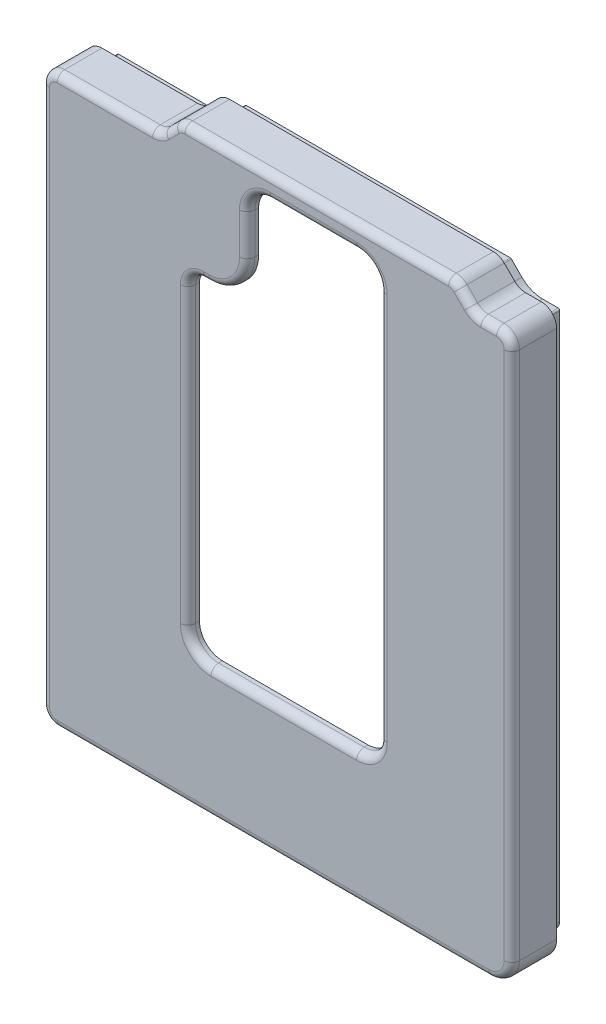
SolidWorks part; units mm, degrees
ref_plane "Front Plane" through (0, 0, 0) normal (0, 0, 1) x (1, 0, 0)
ref_plane "Top Plane" through (0, 0, 0) normal (0, 1, 0) x (1, 0, 0)
ref_plane "Right Plane" through (0, 0, 0) normal (1, 0, 0) x (0, 0, -1)
sketch "ard ref" plane through (0, 0, 0) normal (0, 0, 1) x (1, 0, 0)
  line L0 (2.0155, -3.0374) -> (2.0155, -101.7244) construction
  line L1 (27.0155, -3.0374) -> (27.0155, -101.7244) construction
  line L2 (-17.0643, -59.6174) -> (41.2757, -59.6174) construction
  line L3 (2.0155, -16.358) -> (9.7357, -16.358) construction
  line L4 (27.1007, -75.1174) -> (8.9057, -75.1174)
  line L5 (8.9057, -75.1174) -> (8.9057, -76.6174)
  line L6 (8.9057, -76.6174) -> (27.1007, -76.6174)
  line L7 (27.1007, -76.6174) -> (27.1007, -75.1174)
  line L9 (8.9057, -75.1174) -> (8.9057, -76.6174)
  line L10 (8.9057, -76.6174) -> (27.1007, -76.6174)
  line L11 (27.1007, -76.6174) -> (27.1007, -75.1174)
  line L12 (9.7357, -16.358) -> (9.7357, -0.0374) construction
  line L20 (44.2757, -73.6174) -> (44.2757, -4.5774)
  line L21 (42.2757, -2.5774) -> (40.221, -2.5774)
  line L22 (38.8068, -1.9916) -> (37.4383, -0.6232)
  line L23 (36.0241, -0.0374) -> (1.6013, -0.0374)
  line L24 (0.1871, -0.6232) -> (-1.1814, -1.9916)
  line L25 (-2.5956, -2.5774) -> (-15.0643, -2.5774)
  line L26 (-17.0643, -4.5774) -> (-17.0643, -74.6174)
  line L27 (-15.0643, -76.6174) -> (-4.3943, -76.6174)
  line L28 (-4.3943, -76.6174) -> (-4.3943, -75.1174)
  line L29 (42.7757, -4.0774) -> (42.7757, -75.1174)
  line L30 (42.7757, -4.0774) -> (42.7757, -75.1174)
  line L31 (42.7757, -75.1174) -> (38.1007, -75.1174)
  line L32 (42.7757, -75.1174) -> (38.1007, -75.1174)
  line L33 (-4.3943, -75.1174) -> (-15.5643, -75.1174)
  line L34 (-4.3943, -75.1174) -> (-15.5643, -75.1174)
  line L35 (-15.5643, -75.1174) -> (-15.5643, -4.0774)
  line L36 (-15.5643, -75.1174) -> (-15.5643, -4.0774)
  line L37 (-15.5643, -4.0774) -> (-1.1458, -4.0774)
  line L38 (38.1007, -75.1174) -> (38.1007, -76.6174)
  line L39 (38.1007, -76.6174) -> (41.2757, -76.6174)
  line L40 (44.2757, -73.6174) -> (44.2757, -4.5774)
  line L41 (42.2757, -2.5774) -> (40.221, -2.5774)
  line L42 (38.8068, -1.9916) -> (37.4383, -0.6232)
  line L43 (36.0241, -0.0374) -> (1.6013, -0.0374)
  line L44 (0.1871, -0.6232) -> (-1.1814, -1.9916)
  line L45 (-2.5956, -2.5774) -> (-15.0643, -2.5774)
  line L46 (-17.0643, -4.5774) -> (-17.0643, -74.6174)
  line L47 (-15.0643, -76.6174) -> (-4.3943, -76.6174)
  line L48 (-4.3943, -76.6174) -> (-4.3943, -75.1174)
  line L58 (38.1007, -75.1174) -> (38.1007, -76.6174)
  line L59 (38.1007, -76.6174) -> (41.2757, -76.6174)
  line L77 (27.1007, -75.1174) -> (8.9057, -75.1174)
  line L93 (-15.5643, -4.0774) -> (-1.1458, -4.0774)
  line L94 (-1.1458, -4.0774) -> (1.3942, -1.5374)
  line L95 (-1.1458, -4.0774) -> (1.3942, -1.5374)
  line L96 (1.3942, -1.5374) -> (36.2312, -1.5374)
  line L97 (1.3942, -1.5374) -> (36.2312, -1.5374)
  line L98 (36.2312, -1.5374) -> (38.7712, -4.0774)
  line L99 (36.2312, -1.5374) -> (38.7712, -4.0774)
  line L100 (38.7712, -4.0774) -> (42.7757, -4.0774)
  line L101 (38.7712, -4.0774) -> (42.7757, -4.0774)
  line L103 (38.1007, -73.6174) -> (38.1007, -75.1174)
  line L104 (38.1007, -75.1174) -> (42.7757, -75.1174)
  line L105 (42.7757, -75.1174) -> (42.7757, -4.0774)
  line L106 (42.7757, -4.0774) -> (38.7712, -4.0774)
  line L107 (38.7712, -4.0774) -> (36.2312, -1.5374)
  line L108 (36.2312, -1.5374) -> (1.3942, -1.5374)
  line L109 (1.3942, -1.5374) -> (-1.1458, -4.0774)
  line L110 (-1.1458, -4.0774) -> (-15.5643, -4.0774)
  line L111 (-15.5643, -4.0774) -> (-15.5643, -75.1174)
  line L112 (-15.5643, -75.1174) -> (-4.3943, -75.1174)
  line L113 (-4.3943, -75.1174) -> (-4.3943, -73.6174)
  line L114 (-4.3943, -73.6174) -> (-14.0643, -73.6174)
  line L115 (-14.0643, -73.6174) -> (-14.0643, -5.5774)
  line L116 (-14.0643, -5.5774) -> (-0.5245, -5.5774)
  line L117 (-0.5245, -5.5774) -> (2.0155, -3.0374)
  line L118 (2.0155, -3.0374) -> (35.6099, -3.0374)
  line L119 (35.6099, -3.0374) -> (38.1499, -5.5774)
  line L120 (38.1499, -5.5774) -> (41.2757, -5.5774)
  line L121 (41.2757, -5.5774) -> (41.2757, -73.6174)
  line L122 (41.2757, -73.6174) -> (38.1007, -73.6174)
  line L123 (38.1007, -73.6174) -> (38.1007, -75.1174)
  line L124 (38.1007, -75.1174) -> (42.7757, -75.1174)
  line L125 (42.7757, -75.1174) -> (42.7757, -4.0774)
  line L126 (42.7757, -4.0774) -> (38.7712, -4.0774)
  line L127 (38.7712, -4.0774) -> (36.2312, -1.5374)
  line L128 (36.2312, -1.5374) -> (1.3942, -1.5374)
  line L129 (1.3942, -1.5374) -> (-1.1458, -4.0774)
  line L130 (-1.1458, -4.0774) -> (-15.5643, -4.0774)
  line L131 (-15.5643, -4.0774) -> (-15.5643, -75.1174)
  line L132 (-15.5643, -75.1174) -> (-4.3943, -75.1174)
  line L133 (-4.3943, -75.1174) -> (-4.3943, -73.6174)
  line L134 (-4.3943, -73.6174) -> (-14.0643, -73.6174)
  line L135 (-14.0643, -73.6174) -> (-14.0643, -5.5774)
  line L136 (-14.0643, -5.5774) -> (-0.5245, -5.5774)
  line L137 (-0.5245, -5.5774) -> (2.0155, -3.0374)
  line L138 (2.0155, -3.0374) -> (35.6099, -3.0374)
  line L139 (35.6099, -3.0374) -> (38.1499, -5.5774)
  line L140 (38.1499, -5.5774) -> (41.2757, -5.5774)
  line L141 (41.2757, -5.5774) -> (41.2757, -73.6174)
  line L142 (41.2757, -73.6174) -> (38.1007, -73.6174)
  arc A8 (44.2757, -4.5774) -> (42.2757, -2.5774) centre (42.2757, -4.5774) ccw
  arc A9 (38.8068, -1.9916) -> (40.221, -2.5774) centre (40.221, -0.5774) ccw
  arc A10 (37.4383, -0.6232) -> (36.0241, -0.0374) centre (36.0241, -2.0374) ccw
  arc A11 (1.6013, -0.0374) -> (0.1871, -0.6232) centre (1.6013, -2.0374) ccw
  arc A12 (-2.5956, -2.5774) -> (-1.1814, -1.9916) centre (-2.5956, -0.5774) ccw
  arc A13 (-15.0643, -2.5774) -> (-17.0643, -4.5774) centre (-15.0643, -4.5774) ccw
  arc A14 (-17.0643, -74.6174) -> (-15.0643, -76.6174) centre (-15.0643, -74.6174) ccw
  arc A15 (41.2757, -76.6174) -> (44.2757, -73.6174) centre (41.2757, -73.6174) ccw
  arc A16 (44.2757, -4.5774) -> (42.2757, -2.5774) centre (42.2757, -4.5774) ccw
  arc A17 (38.8068, -1.9916) -> (40.221, -2.5774) centre (40.221, -0.5774) ccw
  arc A18 (37.4383, -0.6232) -> (36.0241, -0.0374) centre (36.0241, -2.0374) ccw
  arc A19 (1.6013, -0.0374) -> (0.1871, -0.6232) centre (1.6013, -2.0374) ccw
  arc A20 (-2.5956, -2.5774) -> (-1.1814, -1.9916) centre (-2.5956, -0.5774) ccw
  arc A21 (-15.0643, -2.5774) -> (-17.0643, -4.5774) centre (-15.0643, -4.5774) ccw
  arc A22 (-17.0643, -74.6174) -> (-15.0643, -76.6174) centre (-15.0643, -74.6174) ccw
  arc A23 (41.2757, -76.6174) -> (44.2757, -73.6174) centre (41.2757, -73.6174) ccw
  dimension "D3" = 25
  dimension "D4" = 17
  dimension "D1" = 0
  dimension "D2" = 0
  dimension "D5" = 0
sketch "Sketch2" plane through (0, 0, 0) normal (0, 0, 1) x (1, 0, 0)
  line L0 (-15.0643, -76.6174) -> (-4.3943, -76.6174) construction
  line L1 (-17.0643, -4.5774) -> (-17.0643, -74.6174) construction
  line L2 (-15.0643, -76.6174) -> (-4.3943, -76.6174)
  line L3 (-17.0643, -4.5774) -> (-17.0643, -74.6174)
  line L4 (-2.5956, -2.5774) -> (-15.0643, -2.5774) construction
  line L5 (36.0241, -0.0374) -> (1.6013, -0.0374) construction
  line L6 (0.1871, -0.6232) -> (-1.1814, -1.9916) construction
  line L7 (44.2757, -73.6174) -> (44.2757, -4.5774) construction
  line L8 (42.2757, -2.5774) -> (40.221, -2.5774) construction
  line L9 (38.8068, -1.9916) -> (37.4383, -0.6232) construction
  line L10 (-2.5956, -2.5774) -> (-15.0643, -2.5774)
  line L11 (36.0241, -0.0374) -> (1.6013, -0.0374)
  line L12 (0.1871, -0.6232) -> (-1.1814, -1.9916)
  line L13 (44.2757, -73.6174) -> (44.2757, -4.5774)
  line L14 (42.2757, -2.5774) -> (40.221, -2.5774)
  line L15 (38.8068, -1.9916) -> (37.4383, -0.6232)
  line L16 (-4.3943, -76.6174) -> (41.2757, -76.6174)
  line L17 (5.0155, -59.6174) -> (24.0155, -59.6174)
  line L18 (2.0155, -3.0374) -> (2.0155, -101.7244) construction
  line L19 (27.0155, -3.0374) -> (27.0155, -101.7244) construction
  line L20 (-17.0643, -59.6174) -> (41.2757, -59.6174) construction
  line L21 (27.0155, -56.6174) -> (27.0155, -6.0374)
  line L22 (24.0155, -3.0374) -> (12.7357, -3.0374)
  line L24 (9.7357, -16.358) -> (9.7357, -0.0374) construction
  line L25 (9.7357, -6.0374) -> (9.7357, -11.358)
  line L26 (4.7357, -16.358) -> (4.0155, -16.358)
  line L27 (2.0155, -18.358) -> (2.0155, -56.6174)
  arc A0 (-17.0643, -74.6174) -> (-15.0643, -76.6174) centre (-15.0643, -74.6174) ccw construction
  arc A1 (-17.0643, -74.6174) -> (-15.0643, -76.6174) centre (-15.0643, -74.6174) ccw
  arc A2 (-15.0643, -2.5774) -> (-17.0643, -4.5774) centre (-15.0643, -4.5774) ccw construction
  arc A3 (-2.5956, -2.5774) -> (-1.1814, -1.9916) centre (-2.5956, -0.5774) ccw construction
  arc A4 (1.6013, -0.0374) -> (0.1871, -0.6232) centre (1.6013, -2.0374) ccw construction
  arc A5 (44.2757, -4.5774) -> (42.2757, -2.5774) centre (42.2757, -4.5774) ccw construction
  arc A6 (37.4383, -0.6232) -> (36.0241, -0.0374) centre (36.0241, -2.0374) ccw construction
  arc A7 (38.8068, -1.9916) -> (40.221, -2.5774) centre (40.221, -0.5774) ccw construction
  arc A8 (41.2757, -76.6174) -> (44.2757, -73.6174) centre (41.2757, -73.6174) ccw construction
  arc A9 (-15.0643, -2.5774) -> (-17.0643, -4.5774) centre (-15.0643, -4.5774) ccw
  arc A10 (-2.5956, -2.5774) -> (-1.1814, -1.9916) centre (-2.5956, -0.5774) ccw
  arc A11 (1.6013, -0.0374) -> (0.1871, -0.6232) centre (1.6013, -2.0374) ccw
  arc A12 (44.2757, -4.5774) -> (42.2757, -2.5774) centre (42.2757, -4.5774) ccw
  arc A13 (37.4383, -0.6232) -> (36.0241, -0.0374) centre (36.0241, -2.0374) ccw
  arc A14 (38.8068, -1.9916) -> (40.221, -2.5774) centre (40.221, -0.5774) ccw
  arc A15 (41.2757, -76.6174) -> (44.2757, -73.6174) centre (41.2757, -73.6174) ccw
  arc A16 (9.7357, -11.358) -> (4.7357, -16.358) centre (4.7357, -11.358) cw
  arc A17 (27.0155, -6.0374) -> (24.0155, -3.0374) centre (24.0155, -6.0374) ccw
  arc A18 (12.7357, -3.0374) -> (9.7357, -6.0374) centre (12.7357, -6.0374) ccw
  arc A19 (24.0155, -59.6174) -> (27.0155, -56.6174) centre (24.0155, -56.6174) ccw
  arc A20 (5.0155, -59.6174) -> (2.0155, -56.6174) centre (5.0155, -56.6174) cw
  arc A21 (4.0155, -16.358) -> (2.0155, -18.358) centre (4.0155, -18.358) ccw
  point P46 (9.7357, -16.358)
  point P49 (27.0155, -3.0374)
  point P52 (9.7357, -3.0374)
  point P55 (27.0155, -59.6174)
  point P58 (2.0155, -59.6174)
  point P61 (2.0155, -16.358)
  dimension "D1" = 5
  dimension "D2" = 3
  dimension "D3" = 2
extrude "Boss-Extrude1" add sketch "Sketch2" along normal blind 1.5
sketch "Sketch3" plane through (0, 0, 0) normal (0, 0, -1) x (-1, 0, 0)
  line L0 (4.3943, -75.1174) -> (4.3943, -73.6174) construction
  line L1 (4.3943, -73.6174) -> (14.0643, -73.6174) construction
  line L2 (14.0643, -73.6174) -> (14.0643, -5.5774) construction
  line L3 (14.0643, -5.5774) -> (0.5245, -5.5774) construction
  line L4 (0.5245, -5.5774) -> (-2.0155, -3.0374) construction
  line L5 (-2.0155, -3.0374) -> (-35.6099, -3.0374) construction
  line L6 (-35.6099, -3.0374) -> (-38.1499, -5.5774) construction
  line L7 (-38.1499, -5.5774) -> (-41.2757, -5.5774) construction
  line L8 (-41.2757, -5.5774) -> (-41.2757, -73.6174) construction
  line L9 (-41.2757, -73.6174) -> (-38.1007, -73.6174) construction
  line L10 (-38.1007, -73.6174) -> (-38.1007, -75.1174) construction
  line L11 (4.3943, -75.1174) -> (4.3943, -73.6174)
  line L12 (4.3943, -73.6174) -> (14.0643, -73.6174)
  line L13 (14.0643, -73.6174) -> (14.0643, -5.5774)
  line L14 (14.0643, -5.5774) -> (0.5245, -5.5774)
  line L15 (0.5245, -5.5774) -> (-2.0155, -3.0374)
  line L16 (-2.0155, -3.0374) -> (-35.6099, -3.0374)
  line L17 (-35.6099, -3.0374) -> (-38.1499, -5.5774)
  line L18 (-38.1499, -5.5774) -> (-41.2757, -5.5774)
  line L19 (-41.2757, -5.5774) -> (-41.2757, -73.6174)
  line L20 (-41.2757, -73.6174) -> (-38.1007, -73.6174)
  line L24 (-38.1007, -73.6174) -> (-38.1007, -75.1174)
  line L25 (-38.1007, -75.1174) -> (-38.1007, -76.6174)
  line L26 (4.3943, -76.6174) -> (15.0643, -76.6174)
  line L27 (4.3943, -75.1174) -> (4.3943, -76.6174)
  line L28 (-8.9057, -76.6174) -> (-8.9057, -73.6174)
  line L29 (-8.9057, -73.6174) -> (-27.0155, -73.6174)
  line L30 (-27.0155, -3.0374) -> (-27.0155, -101.7244) construction
  line L31 (-27.0155, -73.6174) -> (-27.1007, -76.6174)
  line L32 (-27.1007, -76.6174) -> (-8.9057, -76.6174)
  line L33 (17.0643, -74.6174) -> (17.0643, -4.5774)
  line L34 (15.0643, -2.5774) -> (2.5956, -2.5774)
  line L35 (1.1814, -1.9916) -> (-0.1871, -0.6232)
  line L36 (-1.6013, -0.0374) -> (-36.0241, -0.0374)
  line L37 (-37.4383, -0.6232) -> (-38.8068, -1.9916)
  line L38 (-40.221, -2.5774) -> (-42.2757, -2.5774)
  line L39 (-44.2757, -4.5774) -> (-44.2757, -73.6174)
  line L40 (-41.2757, -76.6174) -> (15.0643, -76.6174)
  line L41 (17.0643, -74.6174) -> (17.0643, -4.5774)
  line L42 (15.0643, -2.5774) -> (2.5956, -2.5774)
  line L43 (1.1814, -1.9916) -> (-0.1871, -0.6232)
  line L44 (-1.6013, -0.0374) -> (-36.0241, -0.0374)
  line L45 (-37.4383, -0.6232) -> (-38.8068, -1.9916)
  line L46 (-40.221, -2.5774) -> (-42.2757, -2.5774)
  line L47 (-44.2757, -4.5774) -> (-44.2757, -73.6174)
  line L48 (-41.2757, -76.6174) -> (-38.1007, -76.6174)
  arc A8 (15.0643, -76.6174) -> (17.0643, -74.6174) centre (15.0643, -74.6174) ccw
  arc A9 (17.0643, -4.5774) -> (15.0643, -2.5774) centre (15.0643, -4.5774) ccw
  arc A10 (1.1814, -1.9916) -> (2.5956, -2.5774) centre (2.5956, -0.5774) ccw
  arc A11 (-0.1871, -0.6232) -> (-1.6013, -0.0374) centre (-1.6013, -2.0374) ccw
  arc A12 (-36.0241, -0.0374) -> (-37.4383, -0.6232) centre (-36.0241, -2.0374) ccw
  arc A13 (-40.221, -2.5774) -> (-38.8068, -1.9916) centre (-40.221, -0.5774) ccw
  arc A14 (-42.2757, -2.5774) -> (-44.2757, -4.5774) centre (-42.2757, -4.5774) ccw
  arc A15 (-44.2757, -73.6174) -> (-41.2757, -76.6174) centre (-41.2757, -73.6174) ccw
  arc A16 (15.0643, -76.6174) -> (17.0643, -74.6174) centre (15.0643, -74.6174) ccw
  arc A17 (17.0643, -4.5774) -> (15.0643, -2.5774) centre (15.0643, -4.5774) ccw
  arc A18 (1.1814, -1.9916) -> (2.5956, -2.5774) centre (2.5956, -0.5774) ccw
  arc A19 (-0.1871, -0.6232) -> (-1.6013, -0.0374) centre (-1.6013, -2.0374) ccw
  arc A20 (-36.0241, -0.0374) -> (-37.4383, -0.6232) centre (-36.0241, -2.0374) ccw
  arc A21 (-40.221, -2.5774) -> (-38.8068, -1.9916) centre (-40.221, -0.5774) ccw
  arc A22 (-42.2757, -2.5774) -> (-44.2757, -4.5774) centre (-42.2757, -4.5774) ccw
  arc A23 (-44.2757, -73.6174) -> (-41.2757, -76.6174) centre (-41.2757, -73.6174) ccw
  dimension "D1" = 0
extrude "Boss-Extrude2" add sketch "Sketch3" along normal up to surface (6.55 mm away) contours L32 L28 L29 L31 region at (-5.3755, -74.3674, 0)
sketch "Sketch4" plane through (0, 0, 0) normal (0, 0, -1) x (-1, 0, 0)
  line L1 (-38.1007, -76.6174) -> (-27.0155, -76.6174)
  line L2 (-38.1007, -76.6174) -> (-38.1007, -73.6174)
  line L3 (-38.1007, -73.6174) -> (-27.0155, -73.6174)
  line L4 (-27.0155, -76.6174) -> (-27.0155, -73.6174)
  line L5 (-8.9057, -76.6174) -> (4.3943, -76.6174)
  line L6 (-8.9057, -76.6174) -> (-8.9057, -73.6174)
  line L7 (-8.9057, -73.6174) -> (4.3943, -73.6174)
  line L8 (4.3943, -76.6174) -> (4.3943, -73.6174)
extrude "Boss-Extrude4" add sketch "Sketch4" along normal blind 1
sketch "Sketch6" plane through (0, 0, -6.55) normal (0, 0, -1) x (-1, 0, 0)
  line L0 (-44.2757, -73.6174) -> (-44.2757, -4.5774) construction
  line L1 (17.0643, -4.5774) -> (17.0643, -74.6174) construction
  line L2 (2.5956, -2.5774) -> (15.0643, -2.5774) construction
  line L3 (-0.1871, -0.6232) -> (1.1814, -1.9916) construction
  line L4 (-36.0241, -0.0374) -> (-1.6013, -0.0374) construction
  line L5 (-8.9057, -76.6174) -> (-27.1007, -76.6174) construction
  line L6 (15.0643, -76.6174) -> (4.3943, -76.6174) construction
  line L7 (-38.1007, -76.6174) -> (-41.2757, -76.6174) construction
  line L8 (-42.2757, -2.5774) -> (-40.221, -2.5774) construction
  line L9 (-38.8068, -1.9916) -> (-37.4383, -0.6232) construction
  line L10 (17.0643, -4.5774) -> (17.0643, -74.6174)
  line L11 (2.5956, -2.5774) -> (15.0643, -2.5774)
  line L12 (-0.1871, -0.6232) -> (1.1814, -1.9916)
  line L13 (-36.0241, -0.0374) -> (-1.6013, -0.0374)
  line L14 (-44.2757, -73.6174) -> (-44.2757, -4.5774)
  line L15 (-8.9057, -76.6174) -> (-27.1007, -76.6174)
  line L16 (15.0643, -76.6174) -> (4.3943, -76.6174)
  line L17 (-38.1007, -76.6174) -> (-41.2757, -76.6174)
  line L18 (-42.2757, -2.5774) -> (-40.221, -2.5774)
  line L19 (-38.8068, -1.9916) -> (-37.4383, -0.6232)
  line L22 (-38.1007, -74.8174) -> (-41.2757, -74.8174)
  line L23 (-42.4757, -73.6174) -> (-42.4757, -4.5774)
  line L24 (-42.2757, -4.3774) -> (-40.221, -4.3774)
  line L25 (-37.534, -3.2644) -> (-36.1656, -1.896)
  line L26 (-36.0241, -1.8374) -> (-1.6013, -1.8374)
  line L27 (-1.4599, -1.896) -> (-0.0914, -3.2644)
  line L28 (2.5956, -4.3774) -> (15.0643, -4.3774)
  line L29 (15.2643, -4.5774) -> (15.2643, -74.6174)
  line L30 (15.0643, -74.8174) -> (4.3943, -74.8174)
  line L31 (-38.1007, -74.8174) -> (4.3943, -74.8174)
  line L32 (4.3943, -76.6174) -> (-8.9057, -76.6174)
  line L33 (-27.1007, -76.6174) -> (-38.1007, -76.6174)
  line L34 (-27.0155, -73.6174) -> (-8.9057, -73.6174) construction
  arc A0 (17.0643, -4.5774) -> (15.0643, -2.5774) centre (15.0643, -4.5774) ccw construction
  arc A1 (-0.1871, -0.6232) -> (-1.6013, -0.0374) centre (-1.6013, -2.0374) ccw construction
  arc A2 (-42.2757, -2.5774) -> (-44.2757, -4.5774) centre (-42.2757, -4.5774) ccw construction
  arc A3 (-44.2757, -73.6174) -> (-41.2757, -76.6174) centre (-41.2757, -73.6174) ccw construction
  arc A4 (15.0643, -76.6174) -> (17.0643, -74.6174) centre (15.0643, -74.6174) ccw construction
  arc A5 (-40.221, -2.5774) -> (-38.8068, -1.9916) centre (-40.221, -0.5774) ccw construction
  arc A6 (-36.0241, -0.0374) -> (-37.4383, -0.6232) centre (-36.0241, -2.0374) ccw construction
  arc A7 (17.0643, -4.5774) -> (15.0643, -2.5774) centre (15.0643, -4.5774) ccw
  arc A8 (-0.1871, -0.6232) -> (-1.6013, -0.0374) centre (-1.6013, -2.0374) ccw
  arc A9 (-42.2757, -2.5774) -> (-44.2757, -4.5774) centre (-42.2757, -4.5774) ccw
  arc A10 (-44.2757, -73.6174) -> (-41.2757, -76.6174) centre (-41.2757, -73.6174) ccw
  arc A11 (15.0643, -76.6174) -> (17.0643, -74.6174) centre (15.0643, -74.6174) ccw
  arc A12 (-40.221, -2.5774) -> (-38.8068, -1.9916) centre (-40.221, -0.5774) ccw
  arc A13 (-36.0241, -0.0374) -> (-37.4383, -0.6232) centre (-36.0241, -2.0374) ccw
  arc A14 (1.1814, -1.9916) -> (2.5956, -2.5774) centre (2.5956, -0.5774) ccw construction
  arc A15 (1.1814, -1.9916) -> (2.5956, -2.5774) centre (2.5956, -0.5774) ccw
  arc A16 (-42.4757, -73.6174) -> (-41.2757, -74.8174) centre (-41.2757, -73.6174) ccw
  arc A17 (-42.2757, -4.3774) -> (-42.4757, -4.5774) centre (-42.2757, -4.5774) ccw
  arc A18 (-40.221, -4.3774) -> (-37.534, -3.2644) centre (-40.221, -0.5774) ccw
  arc A19 (-36.0241, -1.8374) -> (-36.1656, -1.896) centre (-36.0241, -2.0374) ccw
  arc A20 (-1.4599, -1.896) -> (-1.6013, -1.8374) centre (-1.6013, -2.0374) ccw
  arc A21 (-0.0914, -3.2644) -> (2.5956, -4.3774) centre (2.5956, -0.5774) ccw
  arc A22 (15.2643, -4.5774) -> (15.0643, -4.3774) centre (15.0643, -4.5774) ccw
  arc A23 (15.0643, -74.8174) -> (15.2643, -74.6174) centre (15.0643, -74.6174) ccw
  dimension "D1" = 1.2
extrude "Cut-Extrude1" cut sketch "Sketch6" against normal blind 2.2
fillet "Fillet1" radius 1 28 edges at (2.6013, -16.9438, 1.5) (2.0155, -37.4877, 1.5) (2.8942, -58.7387, 1.5) (14.5155, -59.6174, 1.5) (26.1368, -58.7387, 1.5) (27.0155, -31.3274, 1.5) (26.1368, -3.9161, 1.5) (18.3756, -3.0374, 1.5) (10.6144, -3.9161, 1.5) (9.7357, -8.6977, 1.5) (8.2712, -14.8936, 1.5) (4.3756, -16.358, 1.5) (-17.0643, -39.5974, 1.5) (-16.4785, -3.1632, 1.5) (-8.8299, -2.5774, 1.5) (-1.8302, -2.4252, 1.5) (-0.4971, -1.3074, 1.5) (0.8359, -0.1896, 1.5) (18.8127, -0.0374, 1.5) (36.7895, -0.1896, 1.5) (38.1226, -1.3074, 1.5) (39.4556, -2.4252, 1.5) (41.2483, -2.5774, 1.5) (43.6899, -3.1632, 1.5) (44.2757, -39.0974, 1.5) (43.397, -75.7387, 1.5) (13.1057, -76.6174, 1.5) (-16.4785, -76.0316, 1.5)
